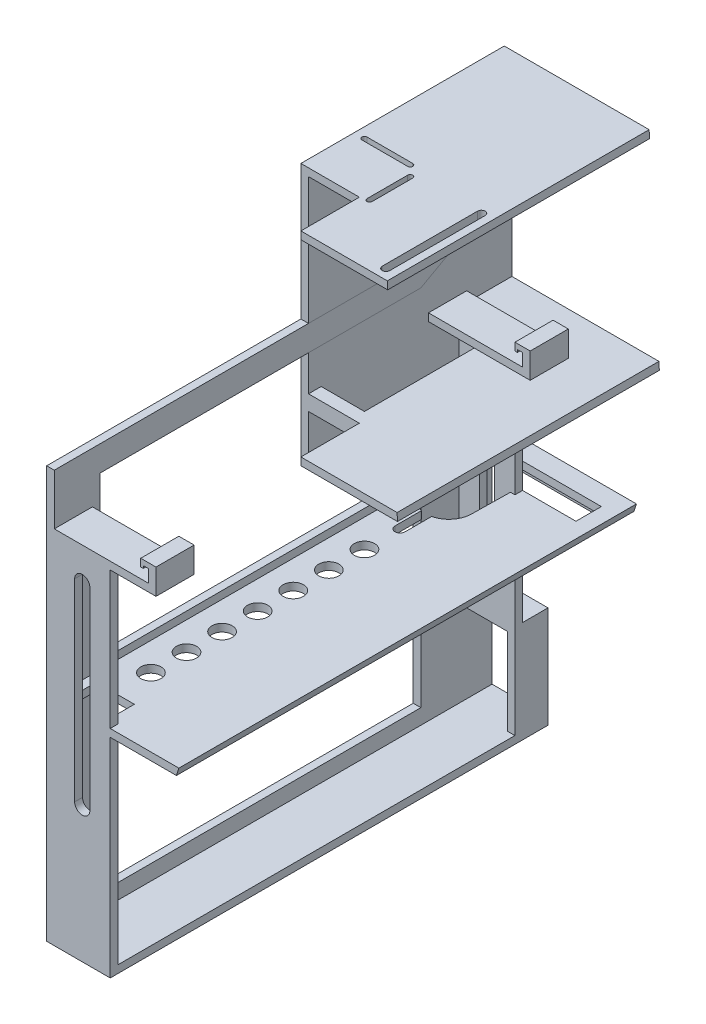
SolidWorks part; units mm, degrees
ref_plane "정면" through (0, 0, 0) normal (0, 0, 1) x (1, 0, 0)
ref_plane "윗면" through (0, 0, 0) normal (0, 1, 0) x (1, 0, 0)
ref_plane "우측면" through (0, 0, 0) normal (1, 0, 0) x (0, 0, -1)
sketch "스케치1" plane through (0, 0, 0) normal (0, 0, 1) x (1, 0, 0)
  line L0 (0, 0) -> (61, 0)
  line L2 (57, 80) -> (0, 80)
  line L3 (0, 80) -> (0, 0)
  line L4 (57.15, 77) -> (3, 77)
  line L5 (3, 77) -> (3, 3)
  line L6 (3, 3) -> (60.85, 3)
  line L9 (61, 0) -> (60.85, 3)
  line L10 (57.15, 77) -> (57, 80)
  line L11 (0, -50) -> (52, -50)
  line L12 (0, -50) -> (0, -135)
  line L13 (0, -135) -> (25, -135)
  line L15 (51.0471, -53) -> (3, -53)
  line L16 (3, -53) -> (3, -132)
  line L17 (3, -132) -> (25.9529, -132)
  line L18 (51.0471, -53) -> (52, -50)
  line L19 (25.9529, -132) -> (25, -135)
  line L20 (0, 140.1376) -> (0, -278.5402) construction
  line L21 (-165.7064, 0) -> (202.0952, 0) construction
  line L22 (0, 0) -> (0, -20)
  line L23 (0, -20) -> (24.5, -20)
  line L24 (24.5, -20) -> (24.5, 0)
  line L25 (24.5, 0) -> (0, 0)
  line L26 (3, -3) -> (3, -17)
  line L27 (3, -17) -> (21.5, -17)
  line L28 (21.5, -17) -> (21.5, -3)
  line L29 (21.5, -3) -> (3, -3)
  line L31 (0, -135) -> (26, -135)
  line L32 (0, -135) -> (0, -50)
  line L33 (0, -50) -> (26, -50)
  line L34 (26, -135) -> (26, -50)
  dimension "D1" = 80
  dimension "D2" = 61
  dimension "D3" = 57
  dimension "D4" = 3
  dimension "D5" = 3
  dimension "D6" = 3
  dimension "D7" = 85
  dimension "D8" = 52
  dimension "D9" = 25
  dimension "D10" = 50
  dimension "D11" = 3
  dimension "D12" = 3
  dimension "D13" = 3
  dimension "D14" = 24.5
  dimension "D15" = 20
  dimension "D16" = 3
extrude "보스-돌출1" add sketch "스케치1" along normal blind 103 contours L6 L9 L0 L3 L2 L10 L4 L5
extrude "보스-돌출2" add sketch "스케치1<3>" along normal blind 180 separate body contours L13 L19 L17 L16 L15 L18 L11 L12
sketch "스케치1<3>" plane through (0, 0, 0) normal (0, 0, 1) x (1, 0, 0) same geometry as "스케치1"
sketch "스케치4" plane through (0, 80, 0) normal (0, 1, 0) x (1, 0, 0)
  line L0 (0, -103) -> (23, -103)
  line L1 (57, -103) -> (0, -103) construction
  line L2 (23, -103) -> (23, -80)
  line L3 (23, -80) -> (0, -80)
  line L4 (0, -103) -> (0, 0) construction
  line L5 (0, -80) -> (0, -103)
  dimension "D1" = 23
  dimension "D2" = 23
extrude "컷-돌출5" cut sketch "스케치4" against normal blind 80
extrude "보스-돌출3" add sketch "스케치1<4>" along normal blind 80 contours L23 L24 L0 L22 L29 L28 L27 L26 region at (12.25, -0.3163, 0)
sketch "스케치1<4>" plane through (0, 0, 0) normal (0, 0, 1) x (1, 0, 0) same geometry as "스케치1"
sketch "스케치5" plane through (0, 3, 0) normal (0, 1, 0) x (1, 0, 0)
  line L0 (3, -75) -> (20, -75)
  line L1 (20, -75) -> (20, -15)
  line L2 (20, -15) -> (3, -15)
  line L3 (3, -15) -> (3, -75)
  line L4 (3, -80) -> (3, 0) construction
  line L5 (23, -80) -> (3, -80) construction
  line L6 (23, -103) -> (23, -80) construction
  dimension "D1" = 5
  dimension "D2" = 3
  dimension "D3" = 60
extrude "컷-돌출6" cut sketch "스케치5" against normal blind 23 contours L1 L2 L3 L0
sketch "스케치6" plane through (0, 80, 0) normal (0, 1, 0) x (1, 0, 0)
  line L0 (3, -80) -> (3, -62)
  line L1 (23, -80) -> (0, -80) construction
  line L2 (3, -62) -> (23, -62)
  line L3 (23, -62) -> (23, -80)
  line L4 (23, -80) -> (3, -80)
  line L5 (26, -63) -> (26, -79) construction
  line L6 (27, -63) -> (27, -79)
  line L7 (25, -63) -> (25, -79)
  line L8 (22, -59) -> (4, -59) construction
  line L9 (22, -60) -> (4, -60)
  line L10 (22, -58) -> (4, -58)
  line L11 (23, -53.8147) -> (23, -84.4922) construction
  line L12 (23, -103) -> (23, -80) construction
  line L13 (49.0843, -62) -> (3.2657, -62) construction
  line L14 (-11.7616, -80) -> (63.6738, -80) construction
  line L18 (0, -80) -> (0, 0) construction
  line L19 (3, -50.2996) -> (3, -101.7053) construction
  arc A0 (27, -63) -> (25, -63) centre (26, -63) ccw
  arc A1 (25, -79) -> (27, -79) centre (26, -79) ccw
  arc A2 (22, -60) -> (22, -58) centre (22, -59) ccw
  arc A3 (4, -58) -> (4, -60) centre (4, -59) ccw
  point P9 (26, -71)
  point P14 (13, -59)
  point P21 (23, -59)
  point P23 (26, -62)
  point P32 (26, -80)
  point P36 (3, -59)
  dimension "D3" = 1
  dimension "D6" = 1
  dimension "D1" = 18
  dimension "D2" = 3
  dimension "D7" = 2
  dimension "D8" = 2
extrude "컷-돌출7" cut sketch "스케치6" against normal blind 23 contours L10 A3 L9 A2 | L6 A1 L7 A0
sketch "스케치7" plane through (0, 80, 0) normal (0, 1, 0) x (1, 0, 0)
  line L0 (52.5, -61.5) -> (52.5, -99) construction
  line L1 (54, -61.5) -> (54, -99)
  line L2 (51, -61.5) -> (51, -99)
  line L3 (57, -103) -> (57, 0) construction
  line L4 (57, -103) -> (23, -103) construction
  line L5 (-4.9645, -60) -> (92.4506, -60) construction
  line L6 (22, -60) -> (4, -60) construction
  arc A0 (54, -61.5) -> (51, -61.5) centre (52.5, -61.5) ccw
  arc A1 (51, -99) -> (54, -99) centre (52.5, -99) ccw
  point P2 (52.5, -80.25)
  dimension "D1" = 1.5
  dimension "D2" = 3
  dimension "D3" = 4
extrude "컷-돌출8" cut sketch "스케치7" against normal blind 23 contours L1 A1 L2 A0
sketch "스케치8" plane through (0, 0, 180) normal (0, 0, 1) x (1, 0, 0)
  line L0 (0, -50) -> (52, -50) construction
  line L1 (0, -135) -> (25, -135)
  line L2 (0, -135) -> (0, -50)
  line L3 (0, -50) -> (25, -50)
  line L4 (25, -135) -> (25, -50)
  dimension "D1" = 25
extrude "보스-돌출4" add sketch "스케치8" against normal blind 5
sketch "스케치9" plane through (0, 0, 180) normal (0, 0, 1) x (1, 0, 0)
  line L0 (0, -135) -> (25, -135) construction
  line L1 (25, -132) -> (25.9529, -132)
  line L2 (25, -132) -> (25, -135)
  line L3 (25, -135) -> (25.9529, -135)
  line L4 (25.9529, -132) -> (25.9529, -135)
extrude "컷-돌출9" cut sketch "스케치9" against normal blind 200
sketch "스케치11" plane through (0, 0, 0) normal (0, 0, -1) x (-1, 0, 0)
  line L1 (-25, -135) -> (0, -135)
  line L2 (-25, -135) -> (-25, -50)
  line L3 (-25, -50) -> (0, -50)
  line L4 (0, -135) -> (0, -50)
sketch "스케치12" plane through (0, -50, 0) normal (0, 1, 0) x (1, 0, 0)
  line L0 (8, -3.3) -> (45.5, -3.3) construction
  line L1 (8, -2) -> (45.5, -2)
  line L2 (8, -4.6) -> (45.5, -4.6)
  line L3 (51.0471, 0) -> (3, 0) construction
  line L4 (0, -180) -> (0, 0) construction
  line L5 (-9.5337, -7.8) -> (64.1799, -7.8) construction
  line L6 (0, 0) -> (26, 0) construction
  arc A0 (8, -2) -> (8, -4.6) centre (8, -3.3) ccw
  arc A1 (45.5, -4.6) -> (45.5, -2) centre (45.5, -3.3) ccw
  point P2 (26.75, -3.3)
  dimension "D3" = 1.3
  dimension "D1" = 2
  dimension "D2" = 8
  dimension "D4" = 37.5
  dimension "D5" = 4.5
extrude "보스-돌출5" add sketch "스케치12" against normal blind 7 contours L2 A1 L1 A0
sketch "스케치13" plane through (0, 0, 0) normal (-1, 0, 0) x (0, 0, 1)
  line L0 (7.8, -33.3991) -> (7.8, -148.5259) construction
  line L1 (0, -135) -> (0, -50) construction
  line L2 (0, 140.1376) -> (0, -278.5402) construction
  line L4 (0, -135) -> (7.8, -135)
  line L5 (0, -135) -> (0, -53)
  line L6 (0, -53) -> (7.8, -53)
  line L7 (7.8, -135) -> (7.8, -53)
  line L8 (7.8, -135) -> (0, -135)
  line L9 (7.8, -135) -> (7.8, -132)
  line L10 (7.8, -132) -> (0, -132)
  line L11 (0, -135) -> (0, -132)
  line M2 (0, -50) -> (0, -135)
  line M3 (0, -135) -> (180, -135)
  dimension "D1" = 7.8
  dimension "D2" = 82
  dimension "D3" = 3
extrude "컷-돌출12" cut sketch "스케치13" against normal blind 25 and the other way through all contours L7 L10 L5 M3 region at (0, -133.5, 3.9)
extrude "컷-돌출14" cut sketch "스케치13<5>" against normal blind 3 and the other way through all contours L10 L7 L6 M2 region at (0, -92.5, 3.9)
sketch "스케치13<5>" plane through (0, 0, 0) normal (-1, 0, 0) x (0, 0, 1) same geometry as "스케치13"
sketch "스케치15" plane through (0, 0, 7.8) normal (0, 0, -1) x (-1, 0, 0)
  line L0 (0, -50) -> (0, -135) construction
  line L1 (-25, -135) -> (0, -135)
  line L2 (-25, -135) -> (-25, -95)
  line L3 (-25, -95) -> (0, -95)
  line L4 (0, -135) -> (0, -95)
  line L5 (-22, -98) -> (-3, -98)
  line L6 (-3, -132) -> (-3, -98)
  line L7 (-22, -132) -> (-3, -132)
  line L8 (-22, -132) -> (-22, -98)
  dimension "D1" = 40
  dimension "D2" = 3
extrude "보스-돌출6" add sketch "스케치15" against normal blind 10
sketch "스케치16" plane through (0, 0, 17.8) normal (0, 0, 1) x (1, 0, 0)
  line L0 (25, -95) -> (25, -132) construction
  line L1 (3, -98) -> (25, -98)
  line L2 (3, -98) -> (3, 2)
  line L3 (3, 2) -> (25, 2)
  line L4 (25, -98) -> (25, 2)
  dimension "D1" = 100
extrude "보스-돌출7" add sketch "스케치16" along normal blind 3
sketch "스케치20" plane through (0, -50, 0) normal (0, 1, 0) x (1, 0, 0)
  line L0 (25, -17.8) -> (3, -17.8) construction
  line L1 (3, -17.8) -> (46, -17.8)
  line L2 (3, -17.8) -> (3, -7.8)
  line L3 (3, -7.8) -> (46, -7.8)
  line L4 (46, -17.8) -> (46, -7.8)
  line L5 (-9.5337, -7.8) -> (64.1799, -7.8) construction
  line L6 (3, -20.8) -> (3, -17.8) construction
  line L7 (52, -180) -> (52, 0) construction
  dimension "D1" = 6
extrude "컷-돌출15" cut sketch "스케치20" against normal blind 3
sketch "스케치21" plane through (0, 0, 17.8) normal (0, 0, -1) x (-1, 0, 0)
  line L0 (-14, -82) -> (-14, -6) construction
  line L1 (-17, -82) -> (-17, -6)
  line L2 (-11, -82) -> (-11, -6)
  line L3 (-3, -98) -> (-3, 2) construction
  line L4 (-3, -95) -> (-25, -95) construction
  line L6 (-3, 2) -> (-25, 2) construction
  arc A0 (-17, -82) -> (-11, -82) centre (-14, -82) ccw
  arc A1 (-11, -6) -> (-17, -6) centre (-14, -6) ccw
  point P2 (-14, -44)
  dimension "D2" = 3
  dimension "D1" = 8
  dimension "D3" = 13
  dimension "D4" = 8
sketch "스케치24" plane through (3, 0, 0) normal (-1, 0, 0) x (0, 0, 1)
  line L1 (20.8, -50) -> (17.8, -50)
  line L2 (20.8, -50) -> (20.8, 2)
  line L3 (20.8, 2) -> (17.8, 2)
  line L4 (17.8, -50) -> (17.8, 2)
extrude "보스-돌출8" add sketch "스케치24" along normal blind 3 contours L2 L3 L4 L1
sketch "스케치25" plane through (0, 0, 180) normal (0, 0, 1) x (1, 0, 0)
  line L1 (0, -135) -> (25, -135)
  line L2 (0, -135) -> (0, 2)
  line L3 (0, 2) -> (25, 2)
  line L4 (25, -135) -> (25, 2)
extrude "보스-돌출9" add sketch "스케치25" against normal blind 3 contours L3 L4 L1 L2
sketch "스케치26" plane through (0, 0, 180) normal (0, 0, 1) x (1, 0, 0)
  line L0 (14, -6) -> (14, -82) construction
  line L1 (17, -6) -> (17, -82)
  line L2 (11, -6) -> (11, -82)
  line L3 (17, -82) -> (17, -6) construction
  arc A0 (17, -6) -> (11, -6) centre (14, -6) ccw
  arc A1 (11, -82) -> (17, -82) centre (14, -82) ccw
  point P4 (14, -44)
sketch "스케치28" plane through (0, -50, 0) normal (0, 1, 0) x (1, 0, 0)
  line L0 (0, -177) -> (25, -177) construction
  line L1 (6.5, -177) -> (21.5, -177)
  line L2 (6.5, -177) -> (6.5, -167)
  line L3 (6.5, -167) -> (21.5, -167)
  line L4 (21.5, -177) -> (21.5, -167)
  line L5 (14, -132.8173) -> (14, -221.1827) construction
  point P9 (14, -177)
  point P10 (14, -177)
  dimension "D1" = 15
  dimension "D2" = 10
extrude "컷-돌출16" cut sketch "스케치28" against normal blind 3 contours L3 L4 L1 L2
sketch "스케치29" plane through (25, 0, 0) normal (1, 0, 0) x (0, 0, -1)
  line L0 (-17.8, -132) -> (-175, -132) construction
  line L1 (-175, -53) -> (-176.9085, -53)
  line L2 (-175, -53) -> (-175, -132)
  line L3 (-175, -132) -> (-176.9085, -132)
  line L4 (-176.9085, -53) -> (-176.9085, -132)
  dimension "D1" = 1.9085
extrude "컷-돌출17" cut sketch "스케치29" against normal blind 22 contours L4 L3 L2 L1
extrude "컷-돌출18" cut sketch "스케치26" against normal blind 10 contours L1 A1 L2 A0
extrude "컷-돌출19" cut sketch "스케치21" against normal blind 10 contours L1 A1 L2 A0
sketch "스케치30" plane through (0, -50, 0) normal (0, 1, 0) x (1, 0, 0)
  line L0 (14, -13.1929) -> (14, -32.0216) construction
  line L1 (11, -20.8) -> (0, -20.8) construction
  line L2 (6.5, -20.8) -> (21.5, -20.8)
  line L3 (6.5, -20.8) -> (6.5, -30.8)
  line L4 (6.5, -30.8) -> (21.5, -30.8)
  line L5 (21.5, -20.8) -> (21.5, -30.8)
  line L6 (3, -17.8) -> (25, -17.8) construction
  point P8 (14, -30.8)
  point P11 (14, -17.8)
  dimension "D1" = 15
  dimension "D2" = 10
extrude "컷-돌출20" cut sketch "스케치30" against normal blind 10 contours L5 L4 L3 L2
sketch "스케치31" plane through (25, 0, 0) normal (1, 0, 0) x (0, 0, -1)
  line L1 (-20.8, -98) -> (-17.8, -98)
  line L2 (-20.8, -98) -> (-20.8, -132)
  line L3 (-20.8, -132) -> (-17.8, -132)
  line L4 (-17.8, -98) -> (-17.8, -132)
extrude "보스-돌출10" add sketch "스케치31" against normal blind 3
sketch "스케치32" plane through (3, 0, 0) normal (1, 0, 0) x (0, 0, -1)
  line L0 (-20.8, 2) -> (-17.8, 2) construction
  line L1 (-177, -50) -> (-20.8, -50)
  line L2 (-177, -50) -> (-177, 2)
  line L3 (-177, 2) -> (-20.8, 2)
  line L4 (-20.8, -50) -> (-20.8, 2)
  line L5 (-177, 2) -> (-180, 2) construction
extrude "보스-돌출11" add sketch "스케치32" against normal blind 3
sketch "스케치35" plane through (0, 2, 0) normal (0, 1, 0) x (1, 0, 0)
  line L0 (25, -20.8) -> (25, -17.8)
  line L1 (25, -17.8) -> (0, -17.8)
  line L2 (0, -17.8) -> (0, -180)
  line L3 (0, -180) -> (25, -180)
  line L4 (25, -180) -> (25, -177)
  line L5 (25, -177) -> (3, -177)
  line L6 (3, -177) -> (3, -20.8)
  line L7 (3, -20.8) -> (25, -20.8)
  line L8 (25, -17.8) -> (46, -17.8) construction
  line L9 (14, -180) -> (49, -180)
  line L10 (14, -180) -> (14, -17.8)
  line L11 (14, -17.8) -> (49, -17.8)
  line L12 (49, -180) -> (49, -17.8)
  point P23 (14, -20.8)
  dimension "D1" = 35
extrude "보스-돌출14" add sketch "스케치35" along normal blind 5 contours L3 L4 L5 L6 L7 L0 L1 L2
sketch "스케치36" plane through (0, 7, 0) normal (0, 1, 0) x (1, 0, 0)
  line L0 (0, -180) -> (25, -180) construction
  line L1 (0, -17.8) -> (3, -17.8)
  line L2 (0, -17.8) -> (0, -180)
  line L3 (0, -180) -> (3, -180)
  line L4 (3, -17.8) -> (3, -180)
  line L5 (3, -177) -> (3, -20.8) construction
extrude "보스-돌출15" add sketch "스케치36" along normal blind 20
sketch "스케치37" plane through (0, 7, 0) normal (0, 1, 0) x (1, 0, 0)
  line L0 (3, -180) -> (25, -180) construction
  line L1 (14, -180) -> (43, -180)
  line L2 (14, -180) -> (14, -17.8)
  line L3 (14, -17.8) -> (43, -17.8)
  line L4 (43, -180) -> (43, -17.8)
  line L5 (25, -17.8) -> (3, -17.8) construction
  line L7 (3, -176.9085) -> (25, -176.9085) construction
  line L9 (3, -180) -> (3, -177) construction
  line L11 (43, -180) -> (40, -180)
  line L12 (43, -180) -> (43, -17.8)
  line L13 (43, -17.8) -> (40, -17.8)
  line L14 (40, -180) -> (40, -17.8)
  point P12 (14, -176.9085)
  dimension "D1" = 40
  dimension "D2" = 3
extrude "보스-돌출16" add sketch "스케치37" against normal blind 3 contours L4 L3 L2 L1
extrude "보스-돌출17" add sketch "스케치37<3>" along normal blind 3 contours L14 L1 L4 L3 region at (41.5, 7, 98.9)
sketch "스케치37<3>" plane through (0, 7, 0) normal (0, 1, 0) x (1, 0, 0) same geometry as "스케치37"
sketch "스케치40" plane through (0, -50, 0) normal (0, 1, 0) x (1, 0, 0)
  line L0 (14, -167) -> (14, 8.9517) construction
  line L1 (6.5, -167) -> (21.5, -167) construction
  line L3 (14, -55) -> (14, -44.7749) construction
  line L5 (12, -55) -> (12, -44.7749)
  line L6 (16, -55) -> (16, -44.7749)
  line L7 (5, -35.7749) -> (4.75, -20.8)
  line L8 (6.5, -20.8) -> (3, -20.8) construction
  line L9 (23, -35.7749) -> (23.25, -20.8)
  line L10 (25, -20.8) -> (21.5, -20.8) construction
  line L11 (23.25, -20.8) -> (4.75, -20.8)
  line L12 (23, -35.7749) -> (5, -35.7749)
  circle A0 centre (14, -153) radius 4
  circle A1 centre (14, -139) radius 4
  circle A2 centre (14, -125) radius 4
  circle A3 centre (14, -111) radius 4
  circle A4 centre (14, -97) radius 4
  circle A5 centre (14, -83) radius 4
  circle A7 centre (14, -35.7749) radius 9
  circle A8 centre (14, -69) radius 4
  arc A9 (12, -55) -> (16, -55) centre (14, -55) ccw
  arc A10 (16, -44.7749) -> (12, -44.7749) centre (14, -44.7749) ccw
  point P20 (14, -49.8875)
  dimension "D1" = 8
  dimension "D2" = 8
  dimension "D3" = 8
  dimension "D4" = 8
  dimension "D5" = 8
  dimension "D6" = 8
  dimension "D13" = 14
  dimension "D14" = 14
  dimension "D15" = 18
  dimension "D17" = 8
  dimension "D16" = 2
  dimension "D7" = 14
  dimension "D8" = 14
  dimension "D9" = 14
  dimension "D10" = 14
  dimension "D11" = 14
  dimension "D12" = 14
extrude "컷-돌출23" cut sketch "스케치40" against normal blind 3 contours A10 A7 L12 | A7 A10 | L6 A10 A7 L5 A9 | A0 | A1 | A2 | A3 | A4 | A5 | A8 | L7 L11 L9 L12 region at (14, -50, 50.644) region at (14, -50, 43.8874) region at (14, -50, 39.3827) region at (14, -50, 153) region at (14, -50, 139) region at (14, -50, 125) region at (14, -50, 111) region at (14, -50, 97) region at (14, -50, 83) region at (14, -50, 69)
sketch "스케치41" plane through (0, 0, 17.8) normal (0, 0, -1) x (-1, 0, 0)
  line L0 (-40, 10) -> (-40, 12)
  line L1 (-40, 12) -> (-38, 12)
  line L2 (-38, 12) -> (-38, 11)
  line L3 (-38, 11) -> (-37, 11)
  line L4 (-37, 11) -> (-37, 14)
  line L5 (-37, 14) -> (-43, 14)
  line L6 (-43, 14) -> (-43, 10)
  line L7 (-43, 4) -> (-43, 10) construction
  line L8 (-43, 10) -> (-40, 10)
  dimension "D1" = 2
  dimension "D2" = 6
  dimension "D3" = 2
  dimension "D4" = 1
  dimension "D5" = 2
extrude "보스-돌출18" add sketch "스케치41" along direction (0, 0, 1) on the side against the normal up to vertex (162.2 mm away) contours L5 L6 L8 L0 L1 L2 L3 L4 up to point (40, 10, 180)
sketch "스케치42" plane through (0, 27, 0) normal (0, 1, 0) x (1, 0, 0)
  line L0 (14, -177) -> (14, -20.8) construction
  line L1 (14, -32.8) -> (43, -32.8)
  line L2 (14, -32.8) -> (14, -165)
  line L3 (14, -165) -> (43, -165)
  line L4 (43, -32.8) -> (43, -165)
  line L5 (43, -180) -> (43, -17.8) construction
  line L7 (40, -17.8) -> (3, -17.8) construction
  line L8 (3, -180) -> (40, -180) construction
  dimension "D1" = 15
  dimension "D2" = 15
extrude "컷-돌출24" cut sketch "스케치42" against normal blind 28
sketch "스케치43" plane through (0, 7, 0) normal (0, 1, 0) x (1, 0, 0)
  line L3 (14, -165) -> (3, -165)
  line L4 (3, -177) -> (3, -165)
  line L5 (3, -180) -> (3, -17.8) construction
  line L6 (14, -165) -> (40, -165) construction
  line L7 (14, -32.8) -> (3, -32.8)
  line L8 (14, -32.8) -> (14, -20.8)
  line L9 (14, -20.8) -> (3, -20.8)
  line L10 (3, -32.8) -> (3, -20.8)
  line L11 (14, -177) -> (3, -177) construction
  line L12 (14, -165) -> (14, -177)
  line L13 (14, -177) -> (3, -177)
extrude "보스-돌출20" add sketch "스케치43" against normal blind 3 contours L3 L4 L13 L12 | L7 L10 L9 L8
sketch "스케치44" plane through (3, 0, 0) normal (1, 0, 0) x (0, 0, -1)
  line L0 (-23.8, -56) -> (-173.9085, -56)
  line L1 (-20.8, -132) -> (-176.9085, -132)
  line L2 (-20.8, -132) -> (-20.8, -53)
  line L3 (-20.8, -53) -> (-176.9085, -53)
  line L4 (-176.9085, -132) -> (-176.9085, -53)
  line L5 (-173.9085, -129) -> (-173.9085, -56)
  line L6 (-23.8, -129) -> (-173.9085, -129)
  line L7 (-23.8, -129) -> (-23.8, -56)
  line L8 (-180, 27) -> (-17.8, 27)
  line L9 (-180, 27) -> (-180, 14)
  line L10 (-180, 14) -> (-165, 14)
  line L11 (-165, 14) -> (-165, 4)
  line L12 (-165, 4) -> (-177, 4)
  line L13 (-177, 4) -> (-177, -50)
  line L14 (-177, -50) -> (-177, 4) construction
  line L15 (-177, 4) -> (-177, -50) construction
  line L16 (-177, -50) -> (-20.8, -50)
  line L17 (-20.8, -50) -> (-20.8, 4)
  line L18 (-20.8, 4) -> (-32.8, 4)
  line L19 (-32.8, 4) -> (-32.8, 14)
  line L20 (-32.8, 14) -> (-17.8, 14)
  line L21 (-17.8, 14) -> (-17.8, 27)
  line L22 (-174, 1) -> (-174, -47)
  line L23 (-174, -47) -> (-23.8, -47)
  line L24 (-23.8, -47) -> (-23.8, 1)
  line L25 (-23.8, 1) -> (-35.8, 1)
  line L26 (-35.8, 1) -> (-35.8, 17)
  line L27 (-35.8, 17) -> (-20.8, 17)
  line L28 (-20.8, 17) -> (-20.8, 24)
  line L29 (-177, 24) -> (-20.8, 24)
  line L30 (-177, 24) -> (-177, 17)
  line L31 (-177, 17) -> (-162, 17)
  line L32 (-162, 17) -> (-162, 1)
  line L33 (-162, 1) -> (-174, 1)
  dimension "D1" = 3
  dimension "D2" = 3
extrude "컷-돌출26" cut sketch "스케치44" against normal blind 10 contours L6 L7 L0 L5 | L29 L28 L27 L26 L25 L24 L23 L22 L33 L32 L31 L30 region at (3, -92.5, 98.8542)
sketch "스케치47" plane through (3, 0, 0) normal (1, 0, 0) x (0, 0, -1)
  line L1 (-177, 24) -> (-20.8, 24)
  line L2 (-177, 24) -> (-177, 17)
  line L3 (-177, 17) -> (-20.8, 17)
  line L4 (-20.8, 24) -> (-20.8, 17)
extrude "보스-돌출21" add sketch "스케치47" against normal blind 3
sketch "스케치48" plane through (0, 0, 0) normal (-1, 0, 0) x (0, 0, 1)
  line L0 (174, -47) -> (23.8, -47) construction
  line L1 (23.8, 1) -> (35.8, 1)
  line L2 (23.8, 1) -> (23.8, -47)
  line L3 (23.8, -47) -> (35.8, -47)
  line L4 (35.8, 1) -> (35.8, -47)
  line L5 (23.8, -129) -> (173.9085, -129) construction
  line L6 (162, 1) -> (174, 1)
  line L7 (162, 1) -> (162, -47)
  line L8 (162, -47) -> (174, -47)
  line L9 (174, 1) -> (174, -47)
  line L10 (23.8, -56) -> (35.8, -56)
  line L11 (23.8, -56) -> (23.8, -129)
  line L12 (23.8, -129) -> (35.8, -129)
  line L13 (35.8, -56) -> (35.8, -129)
  line L14 (23.8, -56) -> (173.9085, -56) construction
  line L15 (162, -56) -> (173.9085, -56)
  line L16 (162, -56) -> (162, -129)
  line L17 (162, -129) -> (173.9085, -129)
  line L18 (173.9085, -56) -> (173.9085, -129)
  line L19 (35.8, 1) -> (35.8, 17) construction
  line L20 (162, 17) -> (162, 1) construction
extrude "보스-돌출22" add sketch "스케치48" against normal blind 3
sketch "스케치49" plane through (3, 0, 0) normal (1, 0, 0) x (0, 0, -1)
  line L0 (-35.8, -129) -> (-35.8, -56) construction
  line L1 (-162, -129) -> (-35.8, -129)
  line L2 (-162, -129) -> (-162, -126)
  line L3 (-162, -126) -> (-35.8, -126)
  line L4 (-35.8, -129) -> (-35.8, -126)
  dimension "D1" = 3
extrude "보스-돌출23" add sketch "스케치49" against normal blind 3 contours L3 L4 L1 L2
